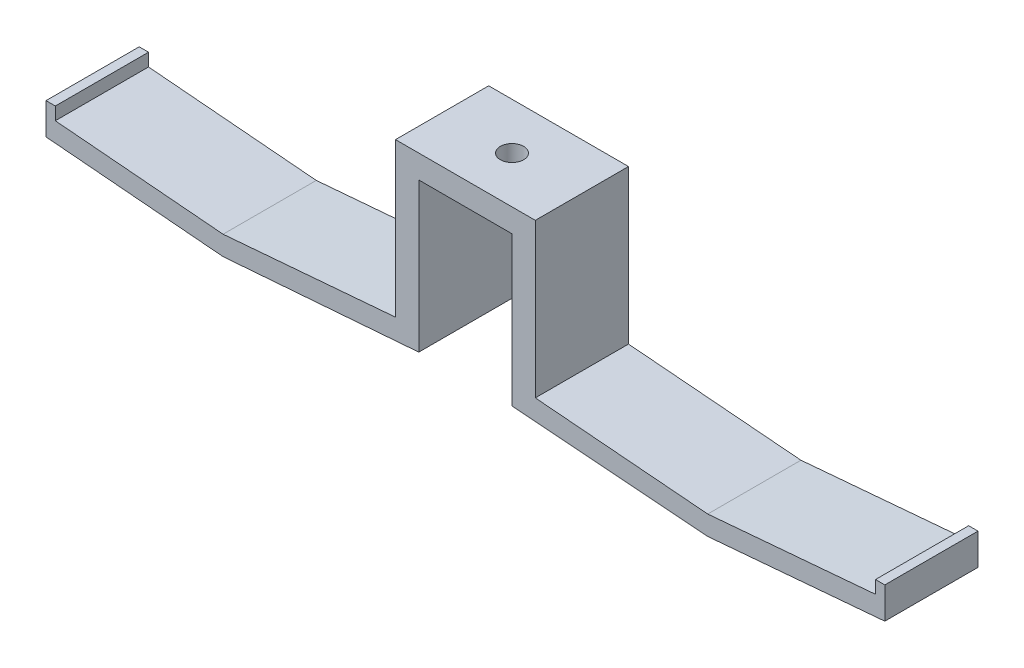
SolidWorks part; units mm, degrees
material "Nylon 6/10"
ref_plane "Front Plane" through (0, 0, 0) normal (0, 0, 1) x (1, 0, 0)
ref_plane "Top Plane" through (0, 0, 0) normal (0, 1, 0) x (1, 0, 0)
ref_plane "Right Plane" through (0, 0, 0) normal (1, 0, 0) x (0, 0, -1)
sketch "Sketch2" plane through (0, 0, 0) normal (0, 0, 1) x (1, 0, 0)
  line L1 (12.7, 0) -> (12.7, -40.64)
  line L2 (12.7, -40.64) -> (66.04, -44.7734)
  line L3 (66.04, -44.7734) -> (114.3, -40.64)
  line L4 (114.3, -40.64) -> (114.3, -32.0734)
  line L5 (111.76, -32.0734) -> (111.76, -35.56)
  line L6 (111.76, -35.56) -> (66.04, -39.4758)
  line L19 (114.3, -32.0734) -> (111.76, -32.0734)
  line L20 (0, 125.2351) -> (0, -75.9356) construction
  line L21 (12.7, 0) -> (-12.7, 0)
  line L22 (0, 0) -> (0, 6.35)
  line L23 (19.05, 6.35) -> (-19.05, 6.35)
  line L24 (19.05, 6.35) -> (19.05, 0)
  line L25 (19.05, 0) -> (19.05, -35.56)
  line L26 (19.05, -35.56) -> (66.04, -39.4758)
  line L27 (-19.05, 0) -> (-19.05, -35.56)
  line L28 (-19.05, 6.35) -> (-19.05, 0)
  line L29 (-12.7, 0) -> (-12.7, -40.64)
  line L30 (-12.7, -40.64) -> (-66.04, -44.7734)
  line L31 (-66.04, -44.7734) -> (-114.3, -40.64)
  line L32 (-114.3, -40.64) -> (-114.3, -32.0734)
  line L33 (-114.3, -32.0734) -> (-111.76, -32.0734)
  line L34 (-111.76, -32.0734) -> (-111.76, -35.56)
  line L35 (-111.76, -35.56) -> (-66.04, -39.4758)
  line L36 (-19.05, -35.56) -> (-66.04, -39.4758)
  dimension "D1" = 19.05
  dimension "D2" = 12.7
  dimension "D3" = 35.56
  dimension "D4" = 3.9158
  dimension "D5" = 40.64
  dimension "D6" = 2.54
  dimension "D7" = 45.72
  dimension "D8" = 46.99
  dimension "D9" = 12.7
  dimension "D10" = 6.35
extrude "Boss-Extrude1" add sketch "Sketch2" along normal blind 25.4 contours L26 L25 L24 L23 L22 L21 L1 L2 L3 L4 L19 L5 L6 | L27 L36 L35 L34 L33 L32 L31 L30 L29 L21 L22 L23 L28 region at (6.35, 1.2521, 0) region at (-6.35, 1.2521, 0)
sketch "Sketch3" plane through (0, 6.35, 0) normal (0, 1, 0) x (1, 0, 0)
  line L0 (19.05, -12.7) -> (-19.05, -12.7) construction
  line L1 (19.05, -25.4) -> (19.05, 0) construction
  line L2 (-19.05, -25.4) -> (-19.05, 0) construction
  circle A0 centre (0, -12.7) radius 3.175
  dimension "D1" = 6.35
extrude "Cut-Extrude1" cut sketch "Sketch3" against normal up to next
